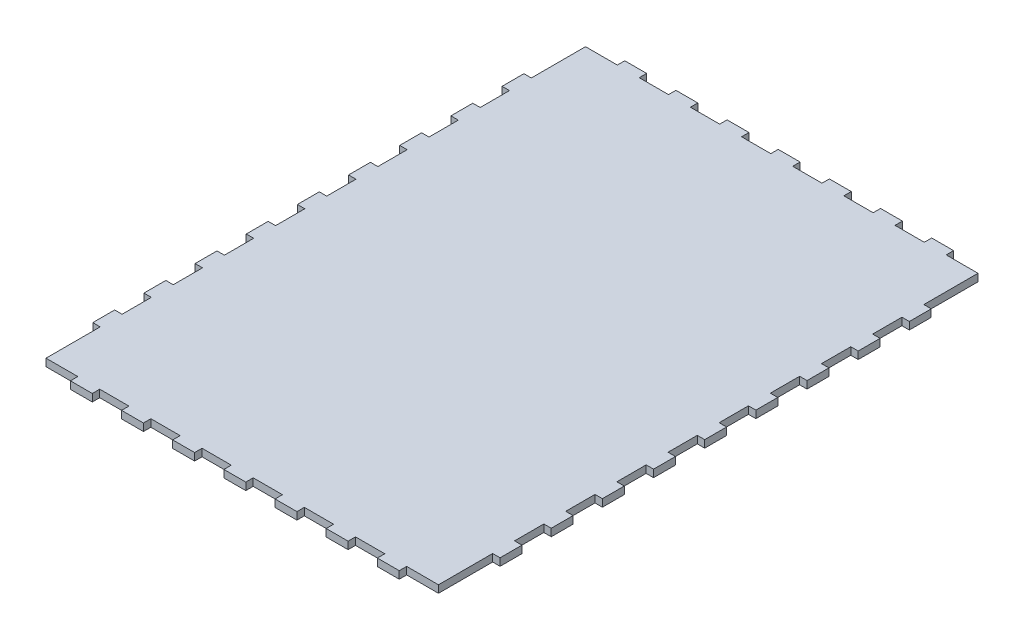
SolidWorks part; units mm, degrees
ref_plane "Front Plane" through (0, 0, 0) normal (0, 0, 1) x (1, 0, 0)
ref_plane "Top Plane" through (0, 0, 0) normal (0, 1, 0) x (1, 0, 0)
ref_plane "Right Plane" through (0, 0, 0) normal (1, 0, 0) x (0, 0, -1)
sketch "Sketch1" plane through (0, 0, 0) normal (0, 1, 0) x (1, 0, 0)
  line L0 (8.3527, -181.1516) -> (28.4047, -181.1516)
  line L1 (-6.6473, 193.5983) -> (8.3527, 193.5983)
  line L2 (205.4135, -144.0205) -> (205.4135, -181.1516)
  line L3 (-26.6993, -181.1516) -> (-6.6473, -181.1516)
  line L5 (-41.6993, -181.1516) -> (-63.5, -181.1516)
  line L6 (63.4567, -181.1516) -> (43.4047, -181.1516)
  line L7 (98.5087, -181.1516) -> (78.4567, -181.1516)
  line L8 (133.5607, -181.1516) -> (113.5087, -181.1516)
  line L9 (210.6983, 3.6854) -> (-96.5701, 3.6854) construction
  line L11 (63.4567, -186.2275) -> (63.4567, -181.1516)
  line L12 (168.6127, -181.1516) -> (148.5607, -181.1516)
  line L13 (78.4567, -186.2275) -> (78.4567, -181.1516)
  line L14 (28.4047, -186.2275) -> (28.4047, -181.1516)
  line L15 (183.6127, -181.1516) -> (205.4135, -181.1516)
  line L16 (43.4047, -186.2275) -> (43.4047, -181.1516)
  line L17 (-6.6473, -186.2275) -> (-6.6473, -181.1516)
  line L18 (63.4567, -186.2275) -> (78.4567, -186.2275)
  line L19 (8.3527, -186.2275) -> (8.3527, -181.1516)
  line L20 (-41.6993, -186.2275) -> (-41.6993, -181.1516)
  line L21 (28.4047, -186.2275) -> (43.4047, -186.2275)
  line L22 (-26.6993, -186.2275) -> (-26.6993, -181.1516)
  line L23 (98.5087, -186.2275) -> (98.5087, -181.1516)
  line L24 (98.5087, -186.2275) -> (113.5087, -186.2275)
  line L25 (113.5087, -186.2275) -> (113.5087, -181.1516)
  line L26 (133.5607, -186.2275) -> (133.5607, -181.1516)
  line L27 (133.5607, -186.2275) -> (148.5607, -186.2275)
  line L28 (148.5607, -186.2275) -> (148.5607, -181.1516)
  line L29 (168.6127, -186.2275) -> (168.6127, -181.1516)
  line L30 (168.6127, -186.2275) -> (183.6127, -186.2275)
  line L31 (183.6127, -186.2275) -> (183.6127, -181.1516)
  line L32 (-41.6993, -186.2275) -> (-26.6993, -186.2275)
  line L33 (-6.6473, -186.2275) -> (8.3527, -186.2275)
  line L34 (-41.6993, 193.5983) -> (-26.6993, 193.5983)
  line L35 (70.9567, -186.2316) -> (70.9567, 200.6271) construction
  line L36 (183.6127, 193.5983) -> (183.6127, 188.5224)
  line L37 (168.6127, 193.5983) -> (183.6127, 193.5983)
  line L38 (168.6127, 193.5983) -> (168.6127, 188.5224)
  line L39 (148.5607, 193.5983) -> (148.5607, 188.5224)
  line L40 (133.5607, 193.5983) -> (148.5607, 193.5983)
  line L41 (133.5607, 193.5983) -> (133.5607, 188.5224)
  line L42 (113.5087, 193.5983) -> (113.5087, 188.5224)
  line L43 (98.5087, 193.5983) -> (113.5087, 193.5983)
  line L44 (98.5087, 193.5983) -> (98.5087, 188.5224)
  line L45 (-26.6993, 193.5983) -> (-26.6993, 188.5224)
  line L46 (28.4047, 193.5983) -> (43.4047, 193.5983)
  line L47 (-41.6993, 193.5983) -> (-41.6993, 188.5224)
  line L48 (8.3527, 193.5983) -> (8.3527, 188.5224)
  line L49 (63.4567, 193.5983) -> (78.4567, 193.5983)
  line L50 (-6.6473, 193.5983) -> (-6.6473, 188.5224)
  line L51 (43.4047, 193.5983) -> (43.4047, 188.5224)
  line L52 (183.6127, 188.5224) -> (205.4135, 188.5224)
  line L53 (28.4047, 193.5983) -> (28.4047, 188.5224)
  line L54 (78.4567, 193.5983) -> (78.4567, 188.5224)
  line L55 (168.6127, 188.5224) -> (148.5607, 188.5224)
  line L56 (63.4567, 193.5983) -> (63.4567, 188.5224)
  line L58 (133.5607, 188.5224) -> (113.5087, 188.5224)
  line L59 (-63.5, 3.6875) -> (-68.58, 3.6875) construction
  line L60 (98.5087, 188.5224) -> (78.4567, 188.5224)
  line L61 (63.4567, 188.5224) -> (43.4047, 188.5224)
  line L62 (-41.6993, 188.5224) -> (-63.5, 188.5224)
  line L63 (-26.6993, 188.5224) -> (-6.6473, 188.5224)
  line L64 (8.3527, 188.5224) -> (28.4047, 188.5224)
  line L65 (-68.58, 11.1875) -> (-63.5, 11.1875)
  line L66 (-68.58, 11.1875) -> (-68.58, -3.8125)
  line L67 (-68.58, -3.8125) -> (-63.5, -3.8125)
  line L68 (210.4935, -144.0205) -> (205.4135, -144.0205)
  line L69 (-68.58, 31.2395) -> (-63.5, 31.2395)
  line L70 (-68.58, 46.2395) -> (-63.5, 46.2395)
  line L71 (-68.58, 46.2395) -> (-68.58, 31.2395)
  line L72 (-68.58, 66.2915) -> (-63.5, 66.2915)
  line L73 (-68.58, 81.2915) -> (-63.5, 81.2915)
  line L74 (-68.58, 81.2915) -> (-68.58, 66.2915)
  line L75 (-68.58, 101.3435) -> (-63.5, 101.3435)
  line L76 (-68.58, 116.3435) -> (-63.5, 116.3435)
  line L77 (-68.58, 116.3435) -> (-68.58, 101.3435)
  line L78 (-68.58, 136.3955) -> (-63.5, 136.3955)
  line L79 (-68.58, 151.3955) -> (-63.5, 151.3955)
  line L80 (-68.58, 151.3955) -> (-68.58, 136.3955)
  line L81 (-68.58, -38.8645) -> (-63.5, -38.8645)
  line L82 (-68.58, -23.8645) -> (-63.5, -23.8645)
  line L83 (-68.58, -23.8645) -> (-68.58, -38.8645)
  line L84 (-68.58, -73.9165) -> (-63.5, -73.9165)
  line L85 (-68.58, -58.9165) -> (-63.5, -58.9165)
  line L86 (-68.58, -58.9165) -> (-68.58, -73.9165)
  line L87 (-68.58, -108.9685) -> (-63.5, -108.9685)
  line L88 (-68.58, -93.9685) -> (-63.5, -93.9685)
  line L89 (-68.58, -93.9685) -> (-68.58, -108.9685)
  line L90 (-68.58, -144.0205) -> (-63.5, -144.0205)
  line L91 (-68.58, -129.0205) -> (-63.5, -129.0205)
  line L92 (-68.58, -129.0205) -> (-68.58, -144.0205)
  line L93 (-63.5, 151.3955) -> (-63.5, 188.5224)
  line L94 (-63.5, 136.3955) -> (-63.5, 116.3435)
  line L95 (-63.5, 101.3435) -> (-63.5, 81.2915)
  line L96 (-63.5, 66.2915) -> (-63.5, 46.2395)
  line L97 (-63.5, 31.2395) -> (-63.5, 11.1875)
  line L98 (-63.5, -3.8125) -> (-63.5, -23.8645)
  line L99 (210.4935, -129.0205) -> (210.4935, -144.0205)
  line L100 (-63.5, -38.8645) -> (-63.5, -58.9165)
  line L101 (-63.5, -73.9165) -> (-63.5, -93.9685)
  line L102 (-63.5, -108.9685) -> (-63.5, -129.0205)
  line L103 (-63.5, -144.0205) -> (-63.5, -181.1516)
  line L104 (210.4935, -129.0205) -> (205.4135, -129.0205)
  line L105 (205.4135, -108.9685) -> (205.4135, -129.0205)
  line L106 (210.4935, -108.9685) -> (205.4135, -108.9685)
  line L107 (210.4935, -93.9685) -> (210.4935, -108.9685)
  line L108 (210.4935, -93.9685) -> (205.4135, -93.9685)
  line L109 (205.4135, -73.9165) -> (205.4135, -93.9685)
  line L110 (210.4935, -73.9165) -> (205.4135, -73.9165)
  line L111 (210.4935, -58.9165) -> (210.4935, -73.9165)
  line L112 (210.4935, -58.9165) -> (205.4135, -58.9165)
  line L113 (205.4135, -38.8645) -> (205.4135, -58.9165)
  line L114 (210.4935, -38.8645) -> (205.4135, -38.8645)
  line L115 (210.4935, -23.8645) -> (210.4935, -38.8645)
  line L116 (210.4935, -23.8645) -> (205.4135, -23.8645)
  line L117 (205.4135, -3.8125) -> (205.4135, -23.8645)
  line L118 (210.4935, -3.8125) -> (205.4135, -3.8125)
  line L119 (210.4935, 11.1875) -> (210.4935, -3.8125)
  line L120 (210.4935, 11.1875) -> (205.4135, 11.1875)
  line L121 (205.4135, 31.2395) -> (205.4135, 11.1875)
  line L122 (210.4935, 31.2395) -> (205.4135, 31.2395)
  line L123 (210.4935, 46.2395) -> (205.4135, 46.2395)
  line L124 (210.4935, 46.2395) -> (210.4935, 31.2395)
  line L125 (205.4135, 66.2915) -> (205.4135, 46.2395)
  line L126 (210.4935, 66.2915) -> (205.4135, 66.2915)
  line L127 (210.4935, 81.2915) -> (205.4135, 81.2915)
  line L128 (205.4135, 101.3435) -> (205.4135, 81.2915)
  line L129 (210.4935, 101.3435) -> (205.4135, 101.3435)
  line L130 (205.4135, 151.3955) -> (205.4135, 188.5224)
  line L131 (205.4135, 136.3955) -> (205.4135, 116.3435)
  line L132 (210.4935, 116.3435) -> (205.4135, 116.3435)
  line L133 (210.4935, 136.3955) -> (205.4135, 136.3955)
  line L134 (210.4935, 151.3955) -> (205.4135, 151.3955)
  line L135 (210.4935, 151.3955) -> (210.4935, 136.3955)
  line L136 (210.4935, 116.3435) -> (210.4935, 101.3435)
  line L137 (210.4935, 81.2915) -> (210.4935, 66.2915)
  dimension "D1" = 15
  dimension "D2" = 5
  dimension "D3" = 5.08
  dimension "D4" = 5
extrude "Boss-Extrude1" add sketch "Sketch1" along normal blind 5.08
